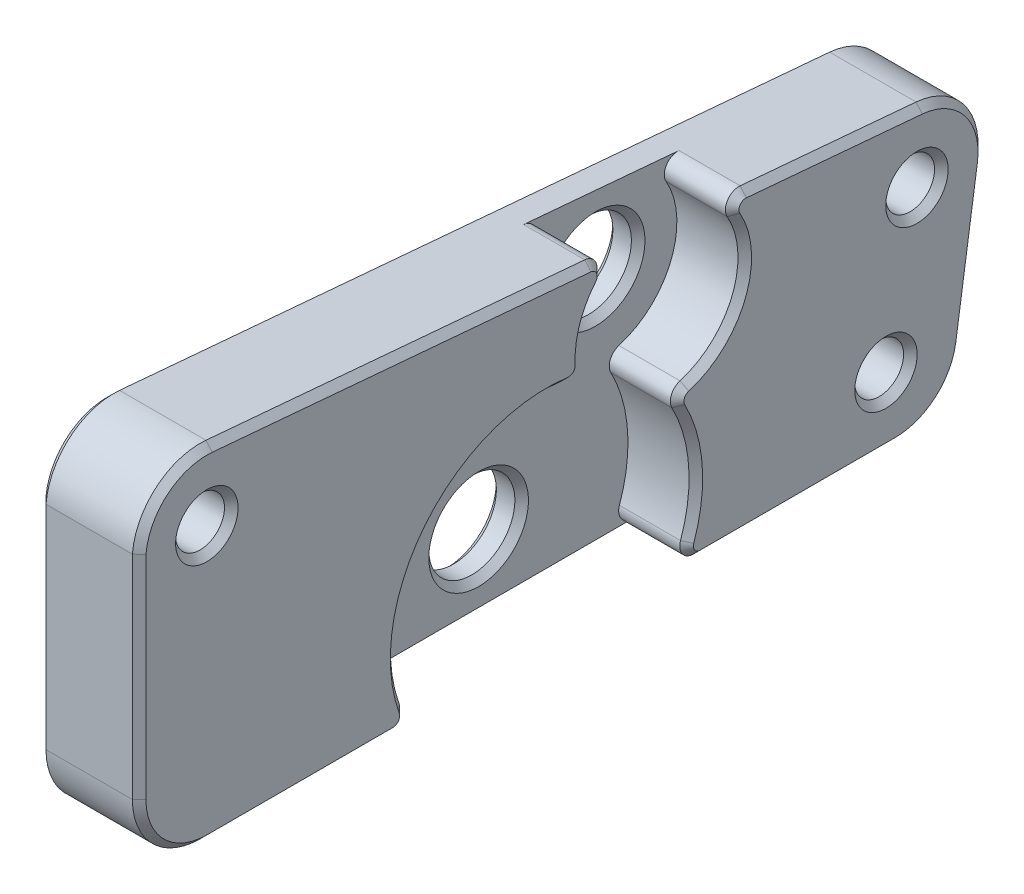
SolidWorks part; units mm, degrees
ref_plane "Front Plane" through (0, 0, 0) normal (0, 0, 1) x (1, 0, 0)
ref_plane "Top Plane" through (0, 0, 0) normal (0, 1, 0) x (1, 0, 0)
ref_plane "Right Plane" through (0, 0, 0) normal (1, 0, 0) x (0, 0, -1)
sketch "Sketch1" plane through (0, 0, 0) normal (0, 1, 0) x (1, 0, 0)
  line L1 (4.675, -38.1) -> (-4.675, -38.1)
  line L2 (4.675, -38.1) -> (4.675, 38.1)
  line L3 (4.675, 38.1) -> (-4.675, 38.1)
  line L4 (-4.675, -38.1) -> (-4.675, 38.1)
  line L5 (4.675, -38.1) -> (-4.675, 38.1) construction
  line L6 (4.675, 38.1) -> (-4.675, -38.1) construction
  point P0 (0, 0)
  point P9 (0, 0)
  dimension "D1" = 9.35
  dimension "D2" = 76.2
extrude "Boss-Extrude3" add sketch "Sketch1" along normal blind 21.59
sketch "Sketch3" plane through (0, 0, 0) normal (0, -1, 0) x (1, 0, 0)
  line L1 (4.675, 38.1) -> (4.675, -38.1) construction
  line L2 (-4.675, 38.1) -> (4.675, 38.1)
  line L3 (-4.675, 38.1) -> (-4.675, -38.1)
  line L4 (-4.675, -38.1) -> (4.675, -38.1)
  line L5 (4.675, 38.1) -> (4.675, -38.1)
  line L6 (-4.675, 38.1) -> (4.675, -38.1) construction
  line L7 (-4.675, -38.1) -> (4.675, 38.1) construction
  line L8 (4.675, -38.1) -> (-4.675, -38.1) construction
  point P3 (0, 0)
  point P4 (0, 0)
extrude "Boss-Extrude4" add sketch "Sketch3" along normal blind 9.525
sketch "Sketch9" plane through (-4.675, 0, 0) normal (-1, 0, 0) x (0, 0, 1)
  line L0 (-38.1, 21.59) -> (-38.1, -9.525)
  line L1 (38.1, -9.525) -> (-38.1, -9.525) construction
  line L2 (-38.1, -9.525) -> (38.1, -9.525)
  line L3 (38.1, 21.59) -> (38.1, -9.525) construction
  line L4 (38.1, -9.525) -> (38.1, 21.59)
  line L5 (-38.1, 3.175) -> (0, 3.175) construction
  line L6 (0, 3.175) -> (25.4, 21.59) construction
  line L7 (0, -3.175) -> (-10.9266, 12.4298) construction
  line L8 (-10.9266, 12.4298) -> (-34.6485, 10.3545) construction
  line L9 (-38.1, 21.59) -> (38.1, 21.59)
  line L10 (-10.9266, 12.4298) -> (31.7728, 16.1656) construction
  line L12 (-38.1, -9.525) -> (-40.9289, 9.4165)
  line L14 (0, -3.175) -> (-31.75, -3.175) construction
  line L15 (-35.202, 16.6803) -> (31.2193, 22.4914)
  circle A0 centre (0, -3.175) radius 4.025
  circle A1 centre (-31.75, -3.175) radius 2.286
  circle A2 centre (31.75, 15.24) radius 2.286 construction
  circle A3 centre (-10.9266, 12.4298) radius 4
  circle A4 centre (-34.6485, 10.3545) radius 2.286
  circle A5 centre (31.7728, 16.1656) radius 2.286
  circle A6 centre (-10.9266, 12.4298) radius 7.62
  circle A7 centre (0, -3.175) radius 13.97
  circle A8 centre (-34.6485, 10.3545) radius 6.35
  circle A9 centre (31.7728, 16.1656) radius 6.35
  line M3 (-38.1, 21.59) -> (-38.1, -9.525)
  line M5 (38.1, -9.525) -> (38.1, 21.59)
  line M6 (38.1, 21.59) -> (-38.1, 21.59)
  dimension "D1" = 8.05
  dimension "D5" = 4.572
  dimension "D6" = 4.572
  dimension "D13" = 8
  dimension "D16" = 4.572
  dimension "D21" = 15.24
  dimension "D22" = 27.94
  dimension "D23" = 12.7
  dimension "D2" = 38.1
  dimension "D3" = 6.35
  dimension "D4" = 31.75
  dimension "D7" = 6.35
  dimension "D8" = 6.35
  dimension "D9" = 38.1
  dimension "D10" = 12.7
  dimension "D11" = 12.7
  dimension "D12" = 19.05
  dimension "D14" = 42.8625
  dimension "D15" = 23.8125
  dimension "D17" = 55
  dimension "D18" = 60
extrude "Cut-Extrude2" cut sketch "Sketch9" against normal through all contours A2 | A4 | A1 | A0 | A5 region at (-4.675, -3.175, 0) region at (-4.675, -3.175, -31.75) region at (-4.675, 10.3545, -34.6485) region at (-4.675, 16.1656, 31.7728)
extrude "Boss-Extrude5" add sketch "Sketch9<10>" against normal up to surface (9.35 mm away) contours A8 L12 M3 | L0 A8 | A9 L15 M6 | L9 A9 region at (-4.675, 10.3545, -39.2856) region at (-4.675, 21.8681, 26.5599) region at (-4.675, 1.0587, -38.9727) region at (-4.675, 21.9626, 31.7728) up to face at (4.675, 16.1656, 34.0588)
sketch "Sketch9<10>" plane through (-4.675, 0, 0) normal (-1, 0, 0) x (0, 0, 1) same geometry as "Sketch9"
extrude "Cut-Extrude8" cut sketch "Sketch9<12>" against normal through all contours A8 L15 A6 L9 M3 | A9 M5 M6 | L15 A6 region at (-4.675, 19.8819, -18.8616) region at (-4.675, 19.2655, -11.5247) region at (-4.675, 20.338, 37.2431)
sketch "Sketch9<12>" plane through (-4.675, 0, 0) normal (-1, 0, 0) x (0, 0, 1) same geometry as "Sketch9"
extrude "Cut-Extrude5" cut sketch "Sketch9<7>" against normal blind 6.35 contours A7 A6 A3 | A6 A7 A0 | A6 A7 L2 A0 | L15 A6 region at (-4.675, 16.2159, -4.5556) region at (-4.675, 19.2655, -11.5247) region at (-4.675, -2.2348, -13.592) region at (-4.675, 7.2907, -7.3282)
sketch "Sketch9<7>" plane through (-4.675, 0, 0) normal (-1, 0, 0) x (0, 0, 1) same geometry as "Sketch9"
extrude "Cut-Extrude6" cut sketch "Sketch9<9>" against normal through all contours A3 region at (-4.675, 12.4298, -10.9266)
sketch "Sketch9<9>" plane through (-4.675, 0, 0) normal (-1, 0, 0) x (0, 0, 1) same geometry as "Sketch9"
fillet "Fillet7" radius 6.35 1 edges at (0, -9.525, -38.1)
fillet "Fillet9" radius 6.35 1 edges at (0, -9.525, 38.1)
chamfer "Chamfer4" distance 0.635 angle 45 8 edges at (4.675, -3.175, 4.025) (4.675, -3.175, -29.464) (-4.675, -3.175, -29.464) (-4.675, 16.1656, 34.0588) (4.675, 16.1656, 34.0588) (-4.675, 10.3545, -32.3625) (4.675, 10.3545, -32.3625) (1.675, -3.175, 4.025)
fillet "Fillet11" radius 1.27 6 edges at (-1.5, -9.525, -12.4434) (-1.5, -9.525, 12.4434) (-1.5, 10.3221, -3.6039) (-1.5, 4.8279, -11.4505) (-1.5, 18.3886, -15.6762) (-1.5, 19.1228, -7.284)
mirror "Mirror2" about plane through (4.675, 21.59, 38.1) normal (-1, 0, 0) of bodies 113 109
delete or keep bodies "Body-Delete/Keep 1" type delete bodies bodies 113
chamfer "Chamfer10" [suppressed] distance 0.635 angle 45
chamfer "Chamfer7" [suppressed] distance 0.635 angle 45
chamfer "Chamfer8" distance 0.635 angle 45 2 edges at (4.675, 12.4298, -6.9266) (7.675, 12.4298, -6.9266)
chamfer "Chamfer9" distance 0.635 angle 45 28 edges at (14.025, 21.0247, 35.8607) (14.025, 20.9415, 13.5035) (14.025, 18.6139, -5.2742) (14.025, 14.8227, -3.6921) (14.025, 10.9939, -2.9131) (14.025, 6.7639, 38.1) (14.025, 5.6415, 10.8365) (14.025, -7.6651, 36.2401) (14.025, -8.9882, 13.3315) (14.025, -9.525, 23.0592) (14.025, 2.6518, -39.9186) (14.025, -7.9853, -36.7732) (14.025, -9.525, -23.4982) (14.025, -8.9882, -13.3315) (14.025, -2.1686, -13.9337) (14.025, 4.4084, -12.3181) (14.025, 9.6126, -18.0067) (14.025, 14.2859, -39.6351) (14.025, 17.5384, -17.567) (14.025, 17.4001, -26.9749) (4.675, 6.7639, 38.1) (4.675, -7.9853, -36.7732) (4.675, -7.6651, 36.2401) (4.675, -9.525, -0.439) (4.675, 19.5858, -1.9913) (4.675, 2.6518, -39.9186) (4.675, 14.2859, -39.6351) (4.675, 21.0247, 35.8607)
